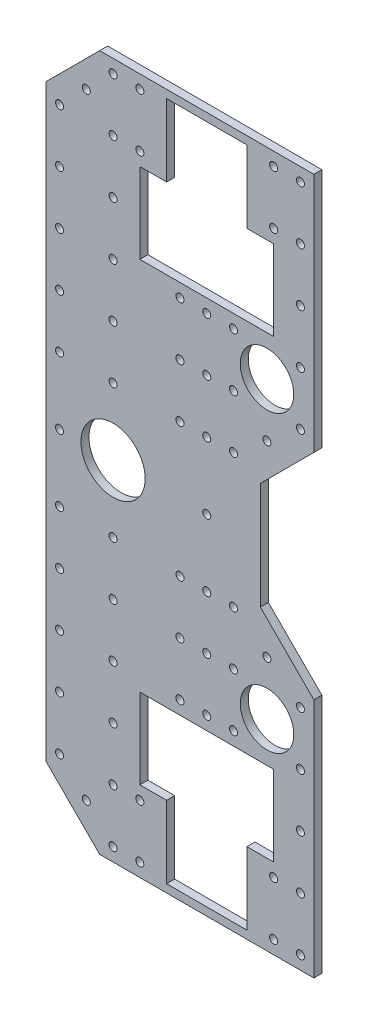
SolidWorks part; units mm, degrees
ref_plane "Front Plane" through (0, 0, 0) normal (0, 0, 1) x (1, 0, 0)
ref_plane "Top Plane" through (0, 0, 0) normal (0, 1, 0) x (1, 0, 0)
ref_plane "Right Plane" through (0, 0, 0) normal (1, 0, 0) x (0, 0, -1)
ref_axis "Axis2" through (0, 55.2999, 0) along (0, -1, 0)
ref_axis "Axis3" through (45, 0, 0) along (-1, 0, 0)
sketch "Sketch1" plane through (0, 0, 0) normal (0, 0, 1) x (1, 0, 0)
  line L0 (-60, 110) -> (-60, 0)
  line L1 (-60, 0) -> (20, 0)
  line L2 (-60, 110) -> (-40, 130)
  line L3 (-40, 130) -> (40, 130)
  line L5 (40, 130) -> (40, 40)
  line L6 (45, 0) -> (-65, 0) construction
  line L7 (40, 40) -> (20, 20)
  line L8 (0, 55.2999) -> (0, -60.0643) construction
  line L9 (-25, 100) -> (-15, 100)
  line L10 (-15, 100) -> (-15, 127)
  line L11 (-25, 100) -> (-25, 70)
  line L12 (-25, 70) -> (25, 70)
  line L13 (25, 100) -> (25, 70)
  line L14 (-15, 127) -> (15, 127)
  line L15 (15, 127) -> (15, 100)
  line L16 (15, 100) -> (25, 100)
  line L17 (20, 20) -> (20, 0)
  point P23 (0, 70)
  dimension "D3" = 20
  dimension "D4" = 25
  dimension "D1" = 110
  dimension "D2" = 130
  dimension "D5" = 28.2843
  dimension "D6" = 60
  dimension "D7" = 20
  dimension "D8" = 80
  dimension "D9" = 20
  dimension "D10" = 90
  dimension "D11" = 3
  dimension "D15" = 25
  dimension "D22" = 30
  dimension "D23" = 70
  dimension "D24" = 27
  dimension "D25" = 30
extrude "Main" add sketch "Sketch1" along normal blind 3
sketch "Sketch2" plane through (0, 0, 3) normal (0, 0, 1) x (1, 0, 0)
  line L0 (45, 0) -> (-65, 0) construction
  line L1 (-60, 110) -> (-60, 0) construction
  line L2 (0, 55.2999) -> (0, -60.0643) construction
  line L3 (-60, 0) -> (20, 0) construction
  line L4 (-60, 110) -> (-60, 0) construction
  circle A0 centre (-35, 0) radius 12
  circle A1 centre (-55, 0) radius 1.5
  circle A2 centre (22.5, 55) radius 10
  circle A3 centre (0, 0) radius 1.5
  circle A4 centre (-45, 115) radius 1.5
  circle A5 centre (22.5, 35) radius 1.5
  point P24 (0, 0)
  dimension "D1" = 24
  dimension "D3" = 3
  dimension "D5" = 22.5
  dimension "D7" = 20
  dimension "D8" = 3
  dimension "D11" = 35
  dimension "D12" = 3
  dimension "D2" = 25
  dimension "D4" = 5
  dimension "D6" = 55
  dimension "D9" = 15
  dimension "D10" = 5
extrude "SingleHoles" cut sketch "Sketch2" against normal through all
sketch "Sketch3" plane through (0, 0, 3) normal (0, 0, 1) x (1, 0, 0)
  circle A0 centre (-35, 125) radius 1.5
  dimension "D1" = 3
  dimension "D2" = 5
  dimension "D3" = 5
extrude "TopLeftHole" cut sketch "Sketch3" against normal through all
pattern_linear "TopLeft2HoleLinearPattern" count 6 spacing 20 along (0, -1, 0) of "TopLeftHole"
sketch "Sketch4" plane through (0, 0, 3) normal (0, 0, 1) x (1, 0, 0)
  line L0 (-60, 110) -> (-60, 0) construction
  circle A0 centre (-35, 105) radius 1.5
  circle A3 centre (-55, 105) radius 1.5
  point P4 (0, 0)
  dimension "D1" = 3
  dimension "D2" = 5
  dimension "D3" = 20
  dimension "D4" = 5
extrude "TopLeft1Hole" cut sketch "Sketch4" against normal through all
pattern_linear "TopLeft1HoleLinearPattern" count 5 spacing 20 along (0, -1, 0) of "TopLeft1Hole"
sketch "Sketch5" plane through (0, 0, 3) normal (0, 0, 1) x (1, 0, 0)
  line L1 (-40, 130) -> (40, 130) construction
  circle A0 centre (35, 125) radius 1.5
  dimension "D1" = 3
  dimension "D2" = 5
  dimension "D3" = 5
extrude "TopRightHole" cut sketch "Sketch5" against normal through all
pattern_linear "TopRightHoleLinearPattern" count 5 spacing 20 along (0, -1, 0) of "TopRightHole"
sketch "MotorHoleFixSketch" plane through (0, 0, 3) normal (0, 0, 1) x (1, 0, 0)
  line L0 (0, 55.2999) -> (0, -60.0643) construction
  line L1 (-60, 0) -> (20, 0) construction
  circle A0 centre (0, 65) radius 1.5
  circle A1 centre (-10, 65) radius 1.5
  circle A2 centre (10, 65) radius 1.5
  point P10 (0, 0)
  dimension "D1" = 3
  dimension "D2" = 65
  dimension "D3" = 10
  dimension "D4" = 10
extrude "MotorHoleFix" cut sketch "MotorHoleFixSketch" against normal through all
pattern_linear "MotorHoleFixLinearPattern" count 3 spacing 20 along (0, -1, 0) of "MotorHoleFix"
sketch "Sketch6" plane through (0, 0, 3) normal (0, 0, 1) x (1, 0, 0)
  line L0 (-40, 130) -> (40, 130) construction
  circle A0 centre (25, 125) radius 1.5
  circle A2 centre (25, 105) radius 1.5
  circle A3 centre (35, 125) radius 1.5 construction
  point P2 (0, 0)
  point P10 (35.0748, 123.6806)
  point P11 (0, 0)
  dimension "D1" = 3
  dimension "D2" = 20
  dimension "D4" = 10
  dimension "D5" = 5
extrude "Cut-Extrude1" cut sketch "Sketch6" against normal through all
mirror "Mirror1" about plane through (0, 0, 0) normal (1, 0, 0) of "Cut-Extrude1"
mirror "LeftRightMirror" about plane through (0, 0, 0) normal (0, 1, 0) of bodies 113 101
